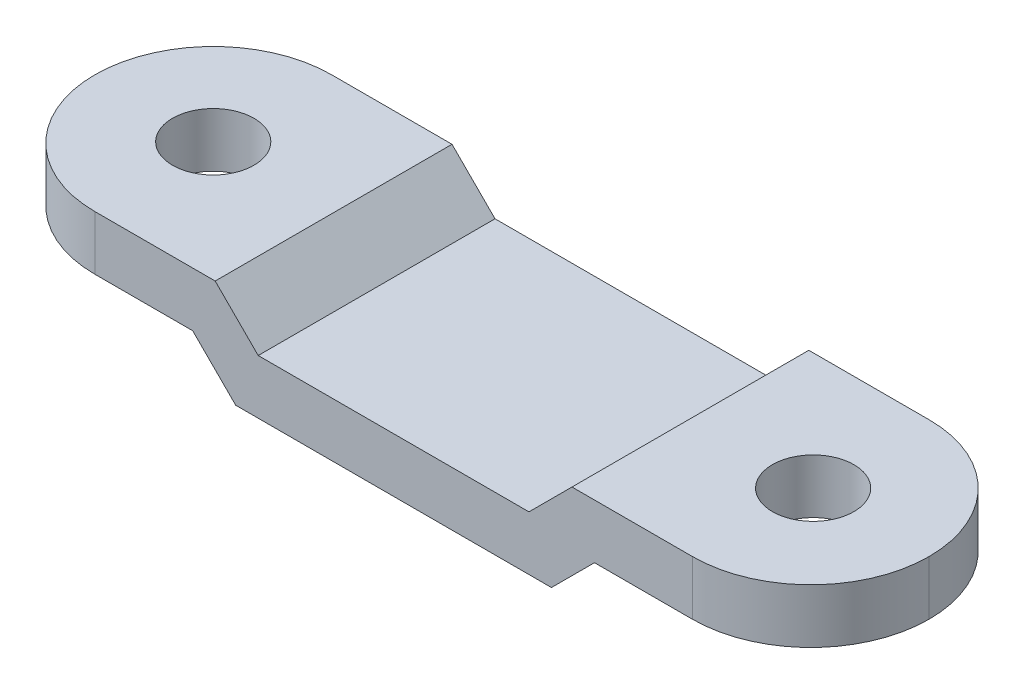
SolidWorks part; units mm, degrees
ref_plane "Plane1" through (0, 0, 0) normal (0, 0, 1) x (1, 0, 0)
ref_plane "Plane2" through (0, 0, 0) normal (0, 1, 0) x (1, 0, 0)
ref_plane "Plane3" through (0, 0, 0) normal (1, 0, 0) x (0, 0, -1)
other "Configuration Table"
sketch "Sketch1" plane through (0, 0, 0) normal (0, 0, 1) x (1, 0, 0)
  line L0 (-8.3421, -2.54) -> (-6.3304, -4.5517)
  line L2 (6.3304, -4.5517) -> (-6.3304, -4.5517)
  line L3 (19.5079, -2.54) -> (8.3421, -2.54)
  line L4 (-8.3421, -2.54) -> (-19.5079, -2.54)
  line L5 (19.5079, -5.08) -> (9.3942, -5.08)
  line L6 (7.3825, -7.0917) -> (-7.3825, -7.0917)
  line L7 (9.3942, -5.08) -> (7.3825, -7.0917)
  line L8 (8.3421, -2.54) -> (6.3304, -4.5517)
  line L9 (0, -16.6659) -> (0, 4.5002) construction
  line L10 (-9.3942, -5.08) -> (-7.3825, -7.0917)
  line L11 (-9.3942, -5.08) -> (-19.5079, -5.08)
  line L12 (19.5079, -5.08) -> (19.5079, -2.54)
  line L13 (-19.5079, -5.08) -> (-19.5079, -2.54)
  point P4 (0, -4.5517)
  dimension "D1" = 135
  dimension "D2" = 2.54
  dimension "D3" = 2.54
  dimension "D4" = 11.1658
  dimension "D5" = 14.765
  dimension "D6" = 2.0117
  dimension "D7" = 2.54
extrude "Base-Extrude" add sketch "Sketch1" along normal blind 11.0744
sketch "Sketch2" plane through (0, -2.54, 0) normal (0, 1, 0) x (-1, 0, 0)
  line L0 (19.5079, 11.0744) -> (19.5079, 0) construction
  circle A0 centre (14.0266, 5.4816) radius 1.905
  circle A1 centre (14.0266, 28.5855) radius 1.905 construction
  point P6 (19.5079, 5.4816)
  dimension "D1" = 5.4813
extrude "Cut-Extrude1" cut sketch "Sketch2" against normal through all
mirror "Mirror1" about plane through (0, 0, 0) normal (1, 0, 0) of "Cut-Extrude1"
fillet "Fillet1" radius 5.5372 4 edges at (19.5079, -3.81, 11.0744) (19.5079, -3.81, 0) (-19.5079, -3.81, 11.0744) (-19.5079, -3.81, 0)
